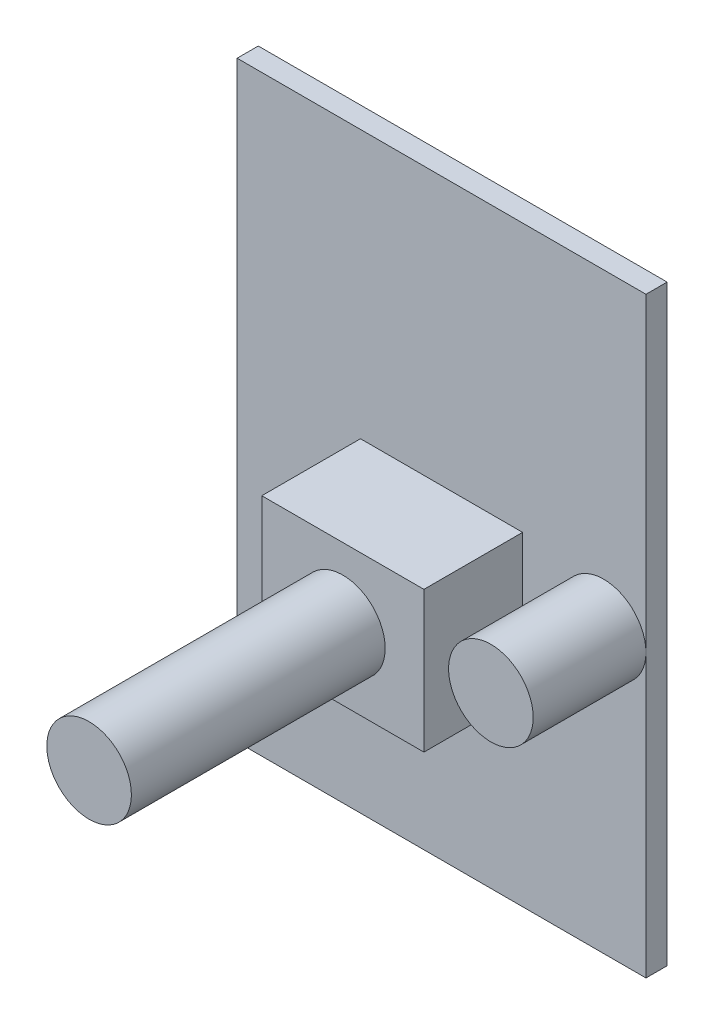
SolidWorks part; units mm, degrees
ref_plane "Front Plane" through (0, 0, 0) normal (0, 0, 1) x (1, 0, 0)
ref_plane "Top Plane" through (0, 0, 0) normal (0, 1, 0) x (1, 0, 0)
ref_plane "Right Plane" through (0, 0, 0) normal (1, 0, 0) x (0, 0, -1)
sketch "Sketch1" plane through (0, 0, 0) normal (0, 0, 1) x (1, 0, 0)
  line L1 (-14.5, 21) -> (14.5, 21)
  line L2 (-14.5, 21) -> (-14.5, -21)
  line L3 (-14.5, -21) -> (14.5, -21)
  line L4 (14.5, 21) -> (14.5, -21)
  line L5 (-14.5, 21) -> (14.5, -21) construction
  line L6 (-14.5, -21) -> (14.5, 21) construction
  point P0 (0, 0)
  dimension "D1" = 42
  dimension "D2" = 29
extrude "Boss-Extrude1" add sketch "Sketch1" along normal blind 1.5
sketch "Sketch2" plane through (0, 0, 1.5) normal (0, 0, 1) x (1, 0, 0)
  line L0 (0, 0) -> (0, -3) construction
  line L1 (-14.5, -21) -> (14.5, -21) construction
  line L2 (-5.75, 2) -> (5.75, 2)
  line L3 (-5.75, 2) -> (-5.75, -8)
  line L4 (-5.75, -8) -> (5.75, -8)
  line L5 (5.75, 2) -> (5.75, -8)
  line L6 (-5.75, 2) -> (5.75, -8) construction
  line L7 (-5.75, -8) -> (5.75, 2) construction
  dimension "D1" = 10
  dimension "D2" = 11.5
  dimension "D3" = 18
extrude "Boss-Extrude2" add sketch "Sketch2" along normal blind 7
sketch "Sketch3" plane through (0, 0, 8.5) normal (0, 0, 1) x (1, 0, 0)
  line L0 (-5.75, -3) -> (5.75, -3) construction
  line L1 (-5.75, 2) -> (-5.75, -8) construction
  line L2 (5.75, -8) -> (5.75, 2) construction
  circle A0 centre (0, -3) radius 3
  dimension "D1" = 6
extrude "Boss-Extrude3" add sketch "Sketch3" along normal blind 18
sketch "Sketch4" plane through (0, 0, 1.5) normal (0, 0, 1) x (1, 0, 0)
  line L2 (5.75, 2) -> (-5.75, 2) construction
  line L3 (14.5, -21) -> (14.5, 21) construction
  circle A0 centre (11.5, -1) radius 3
  dimension "D1" = 6
extrude "Boss-Extrude4" add sketch "Sketch4" along normal blind 8
